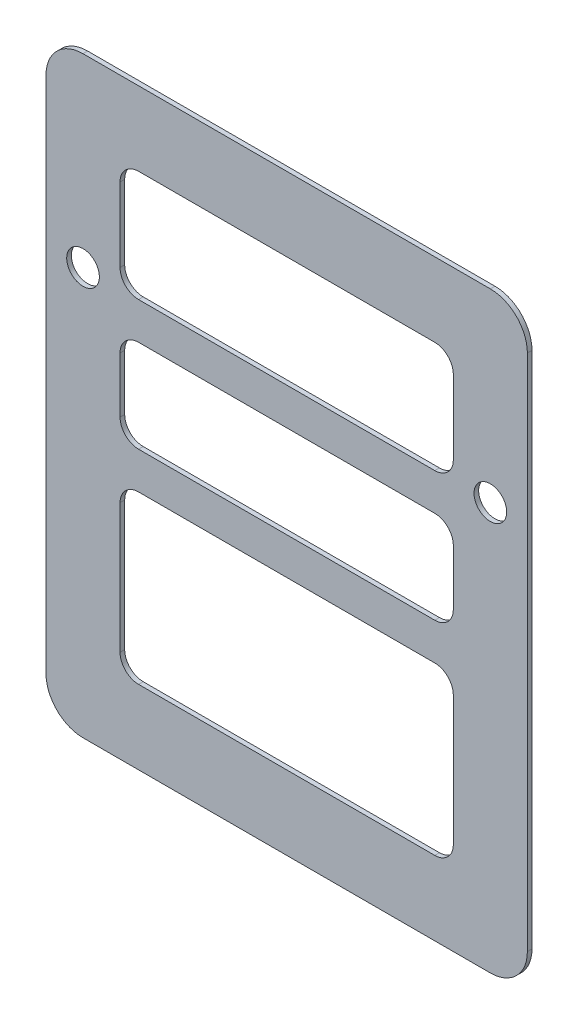
SolidWorks part; units mm, degrees
material "McMaster Carbon Fiber Twill Tube"
ref_plane "Front Plane" through (0, 0, 0) normal (0, 0, 1) x (1, 0, 0)
ref_plane "Top Plane" through (0, 0, 0) normal (0, 1, 0) x (1, 0, 0)
ref_plane "Right Plane" through (0, 0, 0) normal (1, 0, 0) x (0, 0, -1)
sketch "Sketch1" plane through (0, 0, 0) normal (0, 0, 1) x (1, 0, 0)
  line L0 (-165.1, 76.2) -> (-139.7, 76.2) construction
  line L1 (-139.7, -203.2) -> (139.7, -203.2)
  line L2 (-165.1, -177.8) -> (-165.1, 177.8)
  line L3 (-139.7, 203.2) -> (139.7, 203.2)
  line L4 (165.1, -177.8) -> (165.1, 177.8)
  line L5 (-165.1, -203.2) -> (165.1, 203.2) construction
  line L6 (-165.1, 203.2) -> (165.1, -203.2) construction
  line L7 (-139.7, 76.2) -> (139.7, 76.2) construction
  line L8 (139.7, 76.2) -> (165.1, 76.2) construction
  line L10 (-101.6, -152.4) -> (101.6, -152.4)
  line L11 (-114.3, -139.7) -> (-114.3, -50.8)
  line L12 (-101.6, -38.1) -> (101.6, -38.1)
  line L13 (114.3, -139.7) -> (114.3, -50.8)
  line L14 (-101.6, -12.7) -> (101.6, -12.7)
  line L15 (-114.3, 0) -> (-114.3, 38.1)
  line L16 (-101.6, 50.8) -> (101.6, 50.8)
  line L17 (114.3, 0) -> (114.3, 38.1)
  line L18 (-101.6, 152.4) -> (101.6, 152.4)
  line L19 (-114.3, 139.7) -> (-114.3, 88.9)
  line L20 (-101.6, 76.2) -> (101.6, 76.2)
  line L21 (114.3, 139.7) -> (114.3, 88.9)
  circle A0 centre (-139.7, 76.2) radius 11.2
  circle A1 centre (139.7, 76.2) radius 11.2
  arc A2 (-139.7, -203.2) -> (-165.1, -177.8) centre (-139.7, -177.8) cw
  arc A3 (139.7, -203.2) -> (165.1, -177.8) centre (139.7, -177.8) ccw
  arc A4 (139.7, 203.2) -> (165.1, 177.8) centre (139.7, 177.8) cw
  arc A5 (-165.1, 177.8) -> (-139.7, 203.2) centre (-139.7, 177.8) cw
  arc A6 (-114.3, -50.8) -> (-101.6, -38.1) centre (-101.6, -50.8) cw
  arc A7 (-101.6, -152.4) -> (-114.3, -139.7) centre (-101.6, -139.7) cw
  arc A8 (101.6, -152.4) -> (114.3, -139.7) centre (101.6, -139.7) ccw
  arc A9 (101.6, -38.1) -> (114.3, -50.8) centre (101.6, -50.8) cw
  arc A10 (101.6, -12.7) -> (114.3, 0) centre (101.6, 0) ccw
  arc A11 (-101.6, -12.7) -> (-114.3, 0) centre (-101.6, 0) cw
  arc A12 (-114.3, 38.1) -> (-101.6, 50.8) centre (-101.6, 38.1) cw
  arc A13 (101.6, 50.8) -> (114.3, 38.1) centre (101.6, 38.1) cw
  arc A14 (101.6, 76.2) -> (114.3, 88.9) centre (101.6, 88.9) ccw
  arc A15 (101.6, 152.4) -> (114.3, 139.7) centre (101.6, 139.7) cw
  arc A16 (-101.6, 152.4) -> (-114.3, 139.7) centre (-101.6, 139.7) ccw
  arc A17 (-114.3, 88.9) -> (-101.6, 76.2) centre (-101.6, 88.9) ccw
  point P0 (0, 0)
  point P32 (0, 0)
  point P33 (0, 0)
  point P40 (-114.3, -38.1)
  point P45 (114.3, -152.4)
  point P48 (114.3, -38.1)
  point P51 (114.3, -12.7)
  point P54 (-114.3, -12.7)
  point P57 (-114.3, 50.8)
  point P60 (114.3, 50.8)
  point P63 (114.3, 76.2)
  point P70 (-114.3, 76.2)
  dimension "D3" = 22.4
  dimension "D6" = 25.4
  dimension "D15" = 12.7
  dimension "D1" = 406.4
  dimension "D2" = 330.2
  dimension "D4" = 279.4
  dimension "D5" = 127
  dimension "D7" = 50.8
  dimension "D8" = 50.8
  dimension "D9" = 50.8
  dimension "D10" = 114.3
  dimension "D11" = 25.4
  dimension "D12" = 63.5
  dimension "D13" = 50.8
  dimension "D14" = 76.2
extrude "Boss-Extrude1" add sketch "Sketch1" along normal blind 3.175
